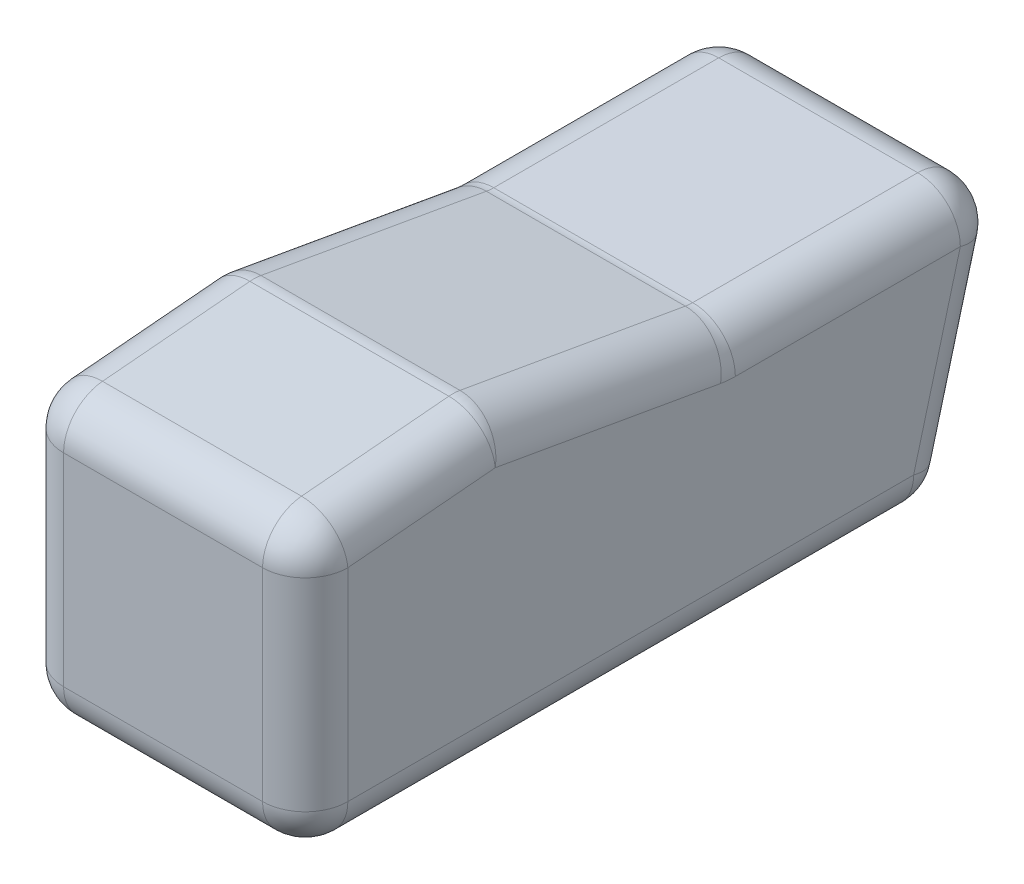
SolidWorks part; units mm, degrees
ref_plane "Ebene vorne" through (0, 0, 0) normal (0, 0, 1) x (1, 0, 0)
ref_plane "Ebene oben" through (0, 0, 0) normal (0, 1, 0) x (1, 0, 0)
ref_plane "Ebene rechts" through (0, 0, 0) normal (1, 0, 0) x (0, 0, -1)
sketch "Skizze2" plane through (0, 0, 0) normal (1, 0, 0) x (0, 0, -1)
  line L0 (1000, -1500) -> (1000, 1500)
  line L1 (-1000, -750) -> (1000, -750) construction
  line L2 (-1000, -750) -> (-1000, 750) construction
  line L3 (-1000, 750) -> (1000, 750) construction
  line L4 (1000, -750) -> (1000, 750) construction
  line L5 (-1000, -750) -> (1000, 750) construction
  line L6 (-1000, 750) -> (1000, -750) construction
  line L7 (1000, 1500) -> (3025, 1677.1645)
  line L8 (3025, 1677.1645) -> (5500, 1240.7553)
  line L9 (5500, 1240.7553) -> (8500, 1240.7553)
  line L10 (8500, 1240.7553) -> (7765.6168, -1500)
  line L11 (7765.6168, -1500) -> (1000, -1500)
  point P0 (0, 0)
  dimension "D1" = 2000
  dimension "D2" = 1500
  dimension "D3" = 7500
  dimension "D4" = 75
  dimension "D5" = 2025
  dimension "D6" = 2475
  dimension "D7" = 95
  dimension "D8" = 165
  dimension "D9" = 750
  dimension "D10" = 750
extrude "Aufsatz-Linear austragen1" add sketch "Skizze2" along normal blind 1500 and the other way blind 1500 contours L8 L9 L10 L11 L0 L7
fillet "Verrundung1" radius 450 18 edges at (-1500, 1240.7553, -7000) (0, 1240.7553, -8500) (1500, 1240.7553, -7000) (-1500, 1458.9599, -4262.5) (0, 1240.7553, -5500) (1500, 1458.9599, -4262.5) (-1500, 1588.5823, -2012.5) (0, 1677.1645, -3025) (1500, 1588.5823, -2012.5) (0, 1500, -1000) (0, -1500, -1000) (-1500, 0, -1000) (-1500, -1500, -4382.8084) (-1500, -129.6224, -8132.8084) (0, -1500, -7765.6168) (1500, -129.6224, -8132.8084) (1500, -1500, -4382.8084) (1500, 0, -1000)
equation "\"hubDiameter\"=1"
